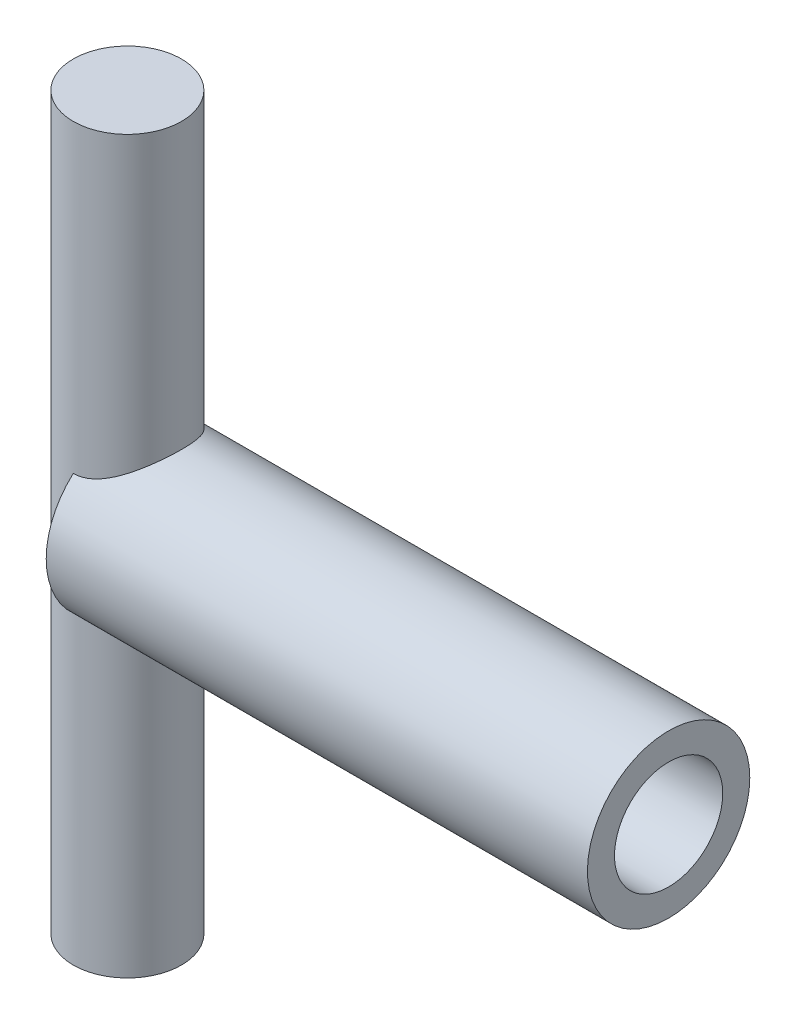
SolidWorks part; units mm, degrees
ref_plane "前视基准面" through (0, 0, 0) normal (0, 0, 1) x (1, 0, 0)
ref_plane "上视基准面" through (0, 0, 0) normal (0, 1, 0) x (1, 0, 0)
ref_plane "右视基准面" through (0, 0, 0) normal (1, 0, 0) x (0, 0, -1)
sketch "草图1" plane through (0, 0, 0) normal (0, 1, 0) x (1, 0, 0)
  circle A0 centre (0, 0) radius 1
extrude "凸台-拉伸1" add sketch "草图1" along normal blind 13.5
ref_plane "基准面1" through (0, 6.75, 0) normal (0, -1, 0) x (-1, 0, 0)
ref_axis "基准轴1" through (0, 13.5, 0) along (0, -1, 0)
ref_point "点1"
ref_plane "基准面2" through (0, 0, 0) normal (1, 0, 0) x (0, 0, -1)
sketch "草图4" plane through (0, 0, 0) normal (1, 0, 0) x (0, 0, -1)
  circle A0 centre (0, 6.75) radius 1.5
  dimension "D1" = 3
extrude "凸台-拉伸3" add sketch "草图4" along normal blind 10
sketch "草图7" plane through (10, 0, 0) normal (1, 0, 0) x (0, 0, -1)
  circle A0 centre (0, 6.75) radius 1
  dimension "D1" = 2
extrude "切除-拉伸15" cut sketch "草图7" against normal blind 9
